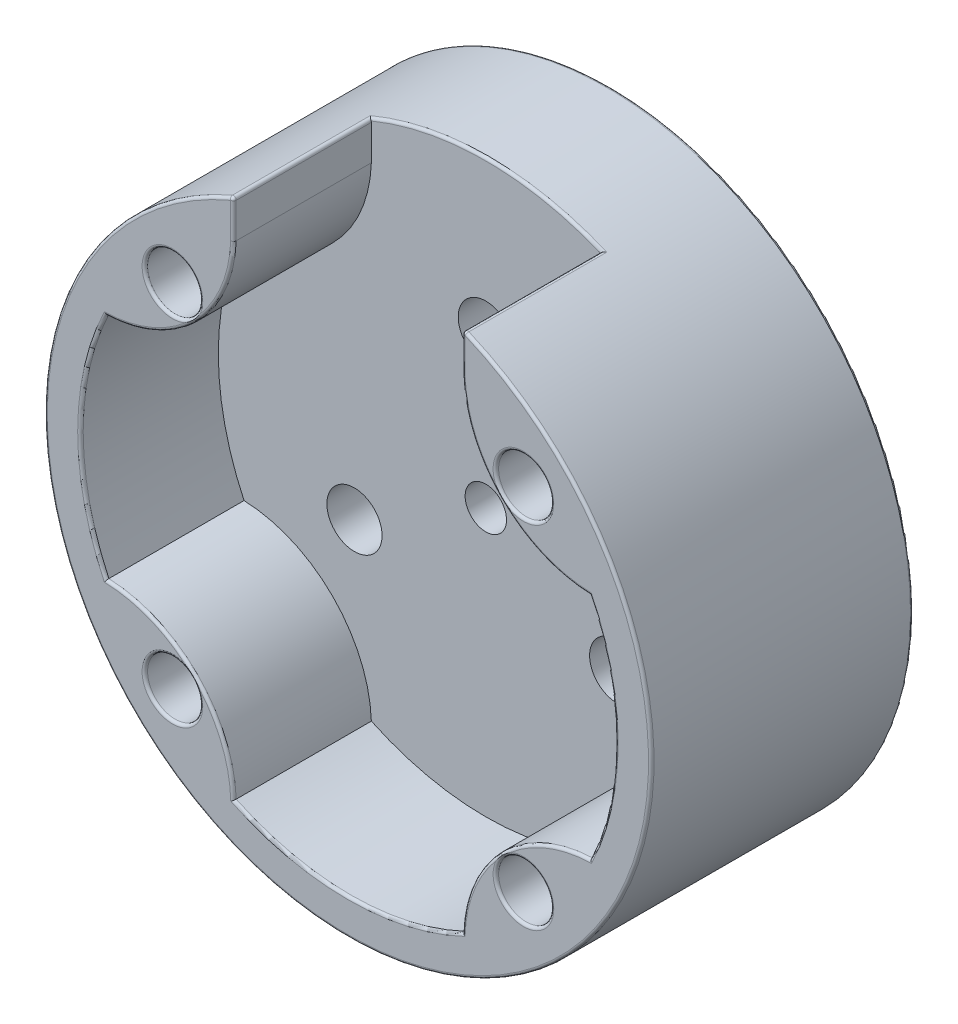
SolidWorks part; units mm, degrees
material "201 Annealed Stainless Steel (SS)"
ref_plane "Front Plane" through (0, 0, 0) normal (0, 0, 1) x (1, 0, 0)
ref_plane "Top Plane" through (0, 0, 0) normal (0, 1, 0) x (1, 0, 0)
ref_plane "Right Plane" through (0, 0, 0) normal (1, 0, 0) x (0, 0, -1)
sketch "Sketch1" plane through (0, 0, 0) normal (0, 0, 1) x (1, 0, 0)
  circle A0 centre (0, 0) radius 11
  dimension "D1" = 22
extrude "Boss-Extrude1" add sketch "Sketch1" along normal blind 9.5
sketch "Sketch2" plane through (0, 0, 9.5) normal (0, 0, 1) x (1, 0, 0)
  line L0 (0, 0) -> (6.364, 6.364) construction
  line L1 (0, 11) -> (0, -11) construction
  line L2 (-11, 0) -> (11, 0) construction
  line L3 (-4.15, 11) -> (-4.15, -11) construction
  line L4 (4.15, 11) -> (4.15, -11) construction
  line L5 (-11, -4.15) -> (11, -4.15) construction
  line L6 (-11, 4.15) -> (11, 4.15) construction
  line L7 (5.5508, 5.5508) -> (5.6569, 5.6569) construction
  line L8 (-4.15, 8.7674) -> (-4.15, 10.1871)
  line L9 (4.15, 8.7674) -> (4.15, 10.1871)
  circle A0 centre (0, 0) radius 11 construction
  circle A1 centre (0, 0) radius 9.7 construction
  circle A2 centre (0, 0) radius 11 construction
  circle A3 centre (0, 0) radius 9 construction
  circle A4 centre (6.364, 6.364) radius 1
  circle A5 centre (6.364, -6.364) radius 1
  circle A6 centre (-6.364, -6.364) radius 1
  circle A7 centre (-6.364, 6.364) radius 1
  arc A8 (4.15, 8.7674) -> (8.7674, 4.15) centre (8.9401, 8.9401) ccw
  arc A9 (8.7674, -4.15) -> (4.15, -8.7674) centre (8.9401, -8.9401) ccw
  arc A10 (-4.15, -8.7674) -> (-8.7674, -4.15) centre (-8.9401, -8.9401) ccw
  arc A11 (-8.7674, 4.15) -> (-4.15, 8.7674) centre (-8.9401, 8.9401) ccw
  arc A12 (-4.15, 10.1871) -> (4.15, 10.1871) centre (0, 0) cw
  arc A13 (-8.7674, 4.15) -> (-8.7494, -4.1879) centre (0, 0) ccw
  arc A14 (-4.15, -8.7674) -> (4.15, -8.7674) centre (0, 0) ccw
  arc A15 (8.7674, -4.15) -> (8.7674, 4.15) centre (0, 0) ccw
  point P17 (0, 0)
  point P33 (5.5508, 5.5508)
  point P45 (0, 0)
  circle M13 centre (0, 0) radius 11
  dimension "D1" = 1.3
  dimension "D2" = 18
  dimension "D3" = 2
  dimension "D4" = 4
  dimension "D9" = 0.15
  dimension "D5" = 4.15
  dimension "D6" = 4.15
  dimension "D7" = 4.15
  dimension "D8" = 4.15
  dimension "D10" = 4
extrude "Cut-Extrude1" cut sketch "Sketch2" against normal blind 5 contours A9 A15 A8 L9 L8 A11 A13 A10 A14 M13 | A7 | A6 | A4 | A5 region at (0, 0.408, 9.5) region at (6.364, 6.364, 9.5) region at (6.364, -6.364, 9.5) region at (-6.364, -6.364, 9.5) region at (-6.364, 6.364, 9.5)
sketch "Sketch3" plane through (0, 0, 0) normal (0, 0, -1) x (-1, 0, 0)
  circle A0 centre (0, 0) radius 0.75
  dimension "D1" = 1.5
extrude "Cut-Extrude2" cut sketch "Sketch3" against normal up to next
fillet "Fillet1" radius 0.1 18 edges at (4.15, 10.1871, 7) (0, 11, 4.5) (-4.15, 10.1871, 7) (11, 0, 0) (-9.7, 0, 9.5) (-5.5508, -5.5508, 9.5) (0, -9.7, 9.5) (5.5508, -5.5508, 9.5) (9.7, 0, 9.5) (5.5508, 5.5508, 9.5) (4.15, 9.4773, 9.5) (0, -11, 9.5) (-4.15, 9.4773, 9.5) (-5.5508, 5.5508, 9.5) (-5.364, 6.364, 9.5) (-5.364, -6.364, 9.5) (7.364, 6.364, 9.5) (7.364, -6.364, 9.5)
sketch "Sketch4" plane through (0, 0, 4.5) normal (0, 0, 1) x (1, 0, 0)
  circle A0 centre (0, 0) radius 5.5 construction
  circle A1 centre (0, 5.5) radius 1
  circle A2 centre (4.7631, -2.75) radius 1
  circle A3 centre (-4.7631, -2.75) radius 1
  point P12 (0, 0)
  dimension "D1" = 11
  dimension "D2" = 2
  dimension "D3" = 3
extrude "Cut-Extrude3" cut sketch "Sketch4" against normal up to next
